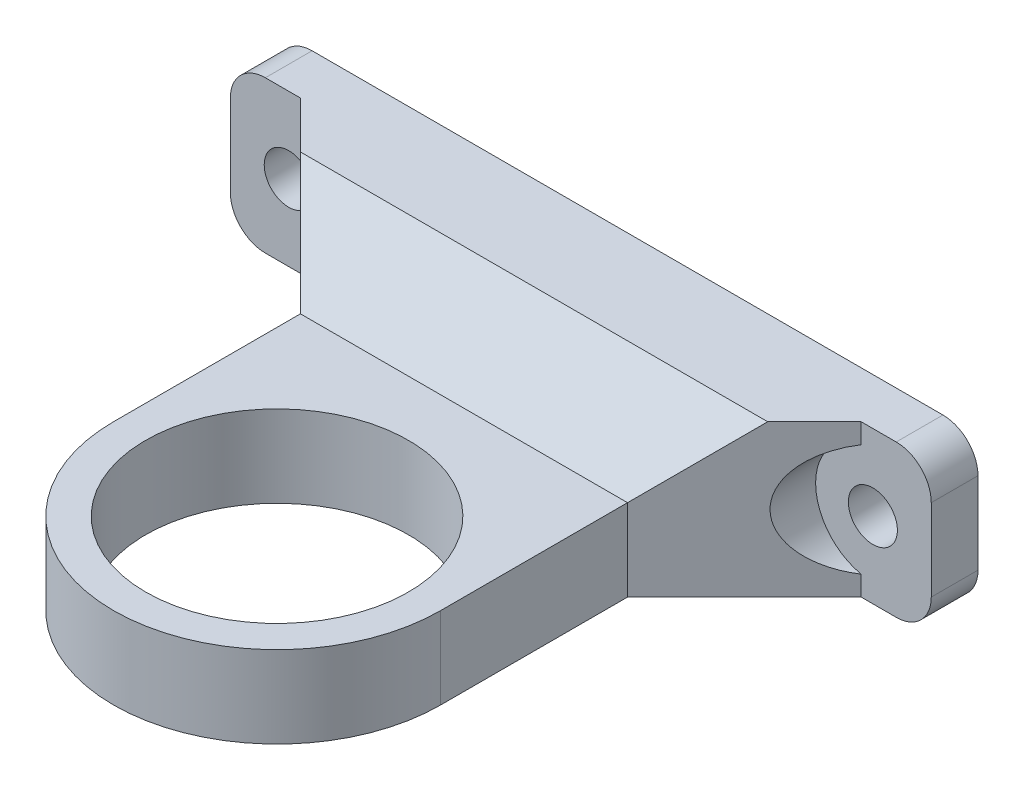
SolidWorks part; units mm, degrees
material "ABS"
ref_plane "Plano frontal" through (0, 0, 0) normal (0, 0, 1) x (1, 0, 0)
ref_plane "Plano superior" through (0, 0, 0) normal (0, 1, 0) x (1, 0, 0)
ref_plane "Plano direito" through (0, 0, 0) normal (1, 0, 0) x (0, 0, -1)
sketch "Esboço1" plane through (0, 0, 0) normal (0, 1, 0) x (1, 0, 0)
  line L0 (0, 22) -> (0, -22) construction
  line L1 (-30, 22) -> (30, 22)
  line L2 (-30, 22) -> (-30, -22)
  line L3 (-30, -22) -> (30, -22)
  line L4 (30, 22) -> (30, -22)
  line L5 (-30, 22) -> (30, -22) construction
  line L6 (-30, -22) -> (30, 22) construction
  line L7 (-14, -8) -> (-14, 18)
  line L8 (-30, 22) -> (30, 22)
  line L9 (-30, 22) -> (-30, 18)
  line L10 (-30, 18) -> (30, 18)
  line L11 (30, 22) -> (30, 18)
  line L12 (14, -8) -> (14, 18)
  circle A0 centre (0, -8) radius 14
  circle A1 centre (0, -8) radius 11.25
  point P0 (0, 0)
  dimension "D2" = 60
  dimension "D3" = 28
  dimension "D4" = 22.5
  dimension "D1" = 44
  dimension "D5" = 4
  dimension "D6" = 30
extrude "Ressalto-extrusão1" add sketch "Esboço1" along normal mid plane 7 contours L2 L10 L4 L1 | A0 L12 L10 L7 | A0 A1 region at (0, 0, -20) region at (0, 0, -10.1724) region at (-9.6195, 0, 17.6195)
sketch "Esboço2" plane through (0, 3.5, 0) normal (0, 1, 0) x (1, 0, 0)
  line L1 (-30, 22) -> (30, 22)
  line L2 (-30, 22) -> (-30, 18)
  line L3 (-30, 18) -> (30, 18)
  line L4 (30, 22) -> (30, 18)
extrude "Ressalto-extrusão2" add sketch "Esboço2" along normal blind 6
chamfer "Chanfro3" distance 10 angle 45 2 edges at (14, 0, -18) (-14, 0, -18)
chamfer "Chanfro5" distance 10 angle 45 1 edges at (0, 3.5, -18)
sketch "Esboço6" plane through (0, 0, -18) normal (0, 0, 1) x (1, 0, 0)
  line L0 (-30, 3) -> (30, 3) construction
  line L1 (-30, 9.5) -> (-30, -3.5) construction
  line L2 (30, 9.5) -> (30, -3.5) construction
  circle A0 centre (-25, 3) radius 2.1
  dimension "D1" = 4.2
  dimension "D2" = 5
extrude "Corte-extrusão2" cut sketch "Esboço6" along direction (0, 0, 1) on the side against the normal through all both and the other way through all
sketch "Esboço7" plane through (0, 0, -18) normal (0, 0, 1) x (1, 0, 0)
  circle A0 centre (-25, 3) radius 4.9
  dimension "D1" = 9.8
extrude "Corte-extrusão6" cut sketch "Esboço7" along normal through all
mirror "Espelhar2" about plane through (0, 0, 0) normal (1, 0, 0) of "Corte-extrusão6", "Corte-extrusão2"
fillet "Filete1" radius 3 4 edges at (30, -3.5, -20) (30, 9.5, -20) (-30, -3.5, -20) (-30, 9.5, -20)
